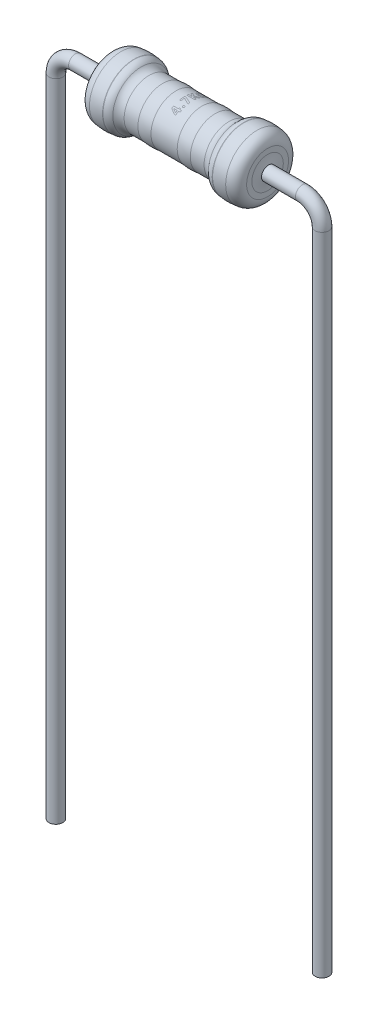
SolidWorks part; units mm, degrees
material "Plain Carbon Steel"
ref_plane "Front Plane" through (0, 0, 0) normal (0, 0, 1) x (1, 0, 0)
ref_plane "Top Plane" through (0, 0, 0) normal (0, 1, 0) x (1, 0, 0)
ref_plane "Right Plane" through (0, 0, 0) normal (1, 0, 0) x (0, 0, -1)
sketch "Sketch1" plane through (0, 0, 0) normal (0, 0, 1) x (1, 0, 0)
  line L0 (-4.33, 0) -> (4.33, 0)
  line L1 (-5.08, -0.75) -> (-5.08, -25.4)
  line L2 (5.08, -0.75) -> (5.08, -25.4)
  line L3 (-5.08, -25.4) -> (5.08, -25.4) construction
  line L4 (0, 0) -> (0, -25.4) construction
  arc A0 (-4.33, 0) -> (-5.08, -0.75) centre (-4.33, -0.75) ccw
  arc A1 (4.33, 0) -> (5.08, -0.75) centre (4.33, -0.75) cw
  dimension "D2" = 0.75
  dimension "D1" = 10.16
  dimension "D3" = 25.4
ref_plane "Plane1" through (-5.08, -25.4, 0) normal (0, -1, 0) x (-1, 0, 0)
sketch "Sketch2" plane through (-5.08, -25.4, 0) normal (0, -1, 0) x (-1, 0, 0)
  circle A0 centre (0, 0) radius 0.265
  dimension "D1" = 0.53
sweep "Sweep1" add profiles "Sketch2" path "Sketch1"
sketch "Sketch3" plane through (0, 0, 0) normal (0, 0, 1) x (1, 0, 0)
  line L0 (-3, 0) -> (3, 0)
  line L5 (-3, 0) -> (-3, 1.2)
  line L6 (3, 0) -> (3, 1.2)
  line L7 (-3, 1.2) -> (-1.75, 1.2)
  line L8 (3, 1.2) -> (1.75, 1.2)
  line L9 (-1.75, 1.2) -> (-1.75, 0.95)
  line L10 (-1.75, 0.95) -> (1.75, 0.95)
  line L11 (1.75, 0.95) -> (1.75, 1.2)
  line L12 (0, 0) -> (0, 0.95) construction
  dimension "D1" = 6
  dimension "D2" = 1.2
  dimension "D3" = 3.5
  dimension "D4" = 0.95
  dimension "D5" = 0.25
revolve "Revolve1" add sketch "Sketch3" angle 360 about L0
fillet "Fillet-1" radius 0.35 2 edges at (1.75, 0, 1.2) (-1.75, 0, 1.2)
fillet "Fillet-2" radius 0.4 4 edges at (3, 0, 1.2) (-3, 0, 1.2) (1.75, 0, 0.95) (-1.75, 0, 0.95)
sketch "Sketch5" plane through (0, 0, 0) normal (0, 0, 1) x (1, 0, 0)
  line L16 (-3, 0) -> (3, 0) construction
  line L17 (-2.6, 1.2) -> (-2.1, 1.2) construction
  line L18 (-2.6, 1.2) -> (-2.6, 0)
  line L19 (-2.6, 0) -> (-2.1, 0)
  line L20 (-2.1, 1.2) -> (-2.1, 0)
  line L21 (-1.75, 0.95) -> (1.75, 0.95) construction
  line L22 (2.6, 1.2) -> (2.1, 1.2) construction
  line L23 (2.6, 1.2) -> (2.6, 0)
  line L24 (2.6, 0) -> (2.1, 0)
  line L25 (2.1, 1.2) -> (2.1, 0)
  line L26 (-0.5, 0.95) -> (-1, 0.95) construction
  line L27 (-0.5, 0.95) -> (-0.5, 0)
  line L28 (-0.5, 0) -> (-1, 0)
  line L29 (-1, 0.95) -> (-1, 0)
  line L30 (-2.35, 1.2) -> (-2.35, 1.22) construction
  line L31 (1, 0.95) -> (0.5, 0.95) construction
  line L32 (1, 0.95) -> (1, 0)
  line L33 (1, 0) -> (0.5, 0)
  line L34 (0.5, 0.95) -> (0.5, 0)
  line L35 (-0.75, 0.95) -> (-0.75, 0.97) construction
  line L36 (0.75, 0.95) -> (0.75, 0.97) construction
  line L37 (2.35, 1.2) -> (2.35, 1.22) construction
  line L48 (-3, 0) -> (-3, 0.6)
  line L49 (-3, 0) -> (-3, 1.2) construction
  line L50 (-3, 0) -> (-3.05, 0)
  line L51 (-3.05, 0) -> (-3.05, 0.2)
  line L52 (3, 0) -> (3.05, 0)
  line L53 (3.05, 0) -> (3.05, 0.2)
  line L54 (3, 0) -> (3, 0.6)
  line L55 (3, 0) -> (3, 1.2) construction
  arc A0 (-2.6, 1.2) -> (-2.1, 1.2) centre (-2.35, -0.3525) cw
  arc A1 (-1, 0.95) -> (-0.5, 0.95) centre (-0.75, -0.6025) cw
  arc A2 (0.5, 0.95) -> (1, 0.95) centre (0.75, -0.6025) cw
  arc A3 (2.1, 1.2) -> (2.6, 1.2) centre (2.35, -0.3525) cw
  arc A6 (-3, 0.6) -> (-3.05, 0.2) centre (-4.625, 0.6) cw
  arc A7 (3.05, 0.2) -> (3, 0.6) centre (4.625, 0.6) cw
  dimension "D4" = 0.02
  dimension "D5" = 0.05
  dimension "D7" = 0.6
  dimension "D1" = 0.5
  dimension "D2" = 0.5
  dimension "D3" = 0.5
  dimension "D6" = 0.2
revolve "Revolve3" add sketch "Sketch5" angle 360 about L19
ref_plane "Plane2" through (0, 2, 0) normal (0, 1, 0) x (1, 0, 0)
sketch "Sketch6" plane through (0, 2, 0) normal (0, 1, 0) x (1, 0, 0)
  line L0 (0, 0) -> (0.15, 0) construction
  line L1 (0.15, 0.95) -> (0.15, -0.95) construction
  line L2 (0.5, 0.95) -> (-0.5, 0.95) construction
  text T0 "4.7KΩ" font "Calibri" height 0.3
  dimension "D1" = 0.15
wrap "Wrap1" sketch "Sketch6" wrap type scribe source sketch "Sketch6" face at (-0.5, -0.95, 0)
